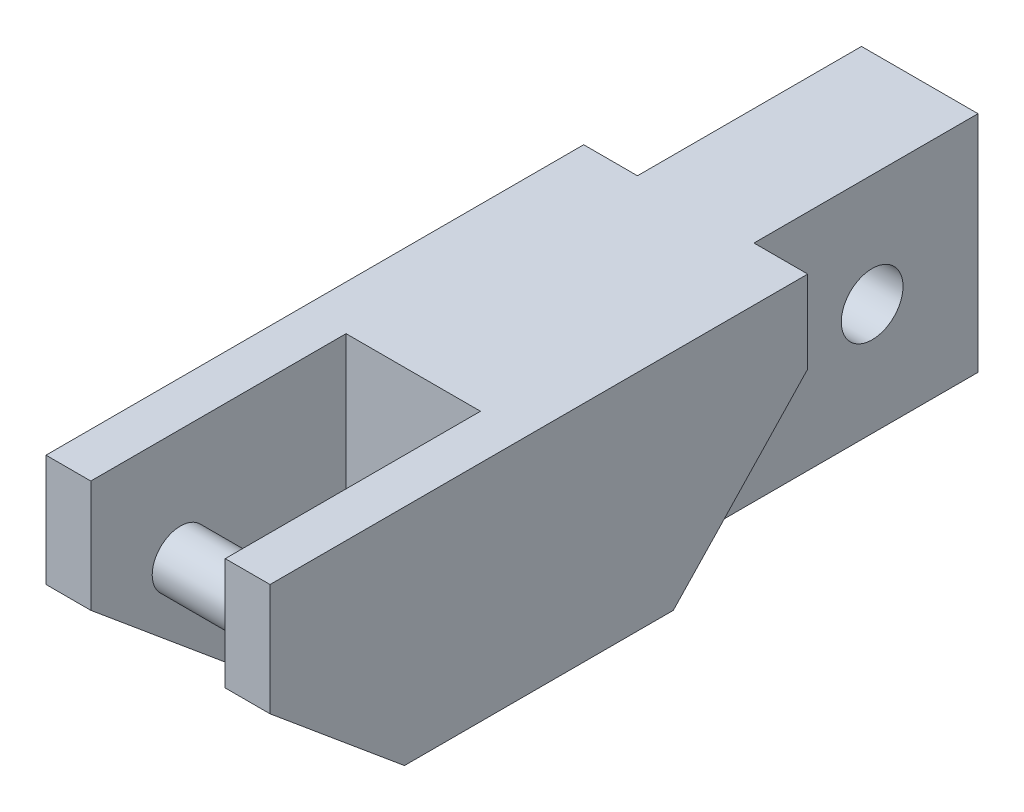
SolidWorks part; units mm, degrees
ref_plane "Front Plane" through (0, 0, 0) normal (0, 0, 1) x (1, 0, 0)
ref_plane "Top Plane" through (0, 0, 0) normal (0, 1, 0) x (1, 0, 0)
ref_plane "Right Plane" through (0, 0, 0) normal (1, 0, 0) x (0, 0, -1)
sketch "Sketch2" plane through (0, 0, 0) normal (0, 1, 0) x (1, 0, 0)
  line L0 (-31.2782, 12.0242) -> (-18.5782, 12.0242)
  line L1 (-28.2302, 24.7242) -> (-21.6262, 24.7242)
  line L2 (-31.2782, 12.0242) -> (-31.2782, -18.4558)
  line L3 (-31.2782, -18.4558) -> (-28.7382, -18.4558)
  line L4 (-18.5782, 12.0242) -> (-18.5782, -18.4558)
  line L5 (-28.2302, 24.7242) -> (-28.2302, 12.0242)
  line L6 (-21.6262, 24.7242) -> (-21.6262, 12.0242)
  line L7 (-28.7382, -18.4558) -> (-28.7382, -3.9858)
  line L8 (-28.7382, -3.9858) -> (-21.1182, -3.9858)
  line L9 (-21.1182, -3.9858) -> (-21.1182, -18.4558)
  line L10 (-31.2782, -3.9858) -> (-18.5782, -3.9858)
  line L11 (-21.1182, -18.4558) -> (-18.5782, -18.4558)
  line L12 (-28.2302, 12.0242) -> (-21.6262, 12.0242)
  dimension "D1" = 43.18
  dimension "D2" = 12.7
  dimension "D3" = 2.54
  dimension "D4" = 2.54
  dimension "D5" = 3.048
  dimension "D6" = 3.048
  dimension "D7" = 12.7
  dimension "D8" = 14.47
extrude "Boss-Extrude1" add sketch "Sketch2" along normal blind 12.7 contours L2 L10 L8 L4 L0 | L6 L1 L5 L0 | L9 L11 L4 L10 | L10 L2 L3 L7 region at (-24.9282, 0, -4.0192) region at (-24.9282, 0, -18.3742) region at (-30.0082, 0, 11.2208) region at (-19.8482, 0, 11.2208)
sketch "Sketch3" plane through (0, 0, 0) normal (1, 0, 0) x (0, 0, -1)
  line L0 (-13.3758, 12.7) -> (-13.3758, 0) construction
  line L1 (12.0242, 12.7) -> (-18.4558, 12.7) construction
  line L2 (12.0242, 0) -> (-18.4558, 0) construction
  line L3 (-18.4558, 12.7) -> (-18.4558, 0) construction
  line L4 (-18.4558, 6.35) -> (24.7242, 6.35) construction
  line L5 (24.7242, 12.7) -> (24.7242, 0) construction
  line L6 (18.7242, 12.7) -> (18.7242, 0) construction
  line L7 (24.7242, 12.7) -> (12.0242, 12.7) construction
  line L8 (24.7242, 0) -> (12.0242, 0) construction
  circle A0 centre (-13.3758, 6.35) radius 1.6
  circle A1 centre (18.7242, 6.35) radius 1.75
  dimension "D1" = 5.08
  dimension "D2" = 6
extrude "Cut-Extrude1" cut sketch "Sketch3" against normal through all contours A1
extrude "Boss-Extrude4" add sketch "Sketch3<3>" against normal through all from surface contours A0 starting at face at (-18.5782, 6.35, 3.2158)
sketch "Sketch3<3>" plane through (0, 0, 0) normal (1, 0, 0) x (0, 0, -1) same geometry as "Sketch3"
sketch "Sketch29" plane through (-18.5782, 0, 0) normal (1, 0, 0) x (0, 0, -1)
  line L0 (-18.4373, 6.3346) -> (38392.6267, -32002.8854) construction
  line L1 (-18.4558, 12.7) -> (-18.4558, 0) construction
  line L3 (-18.4558, 6.35) -> (-10.8358, 0)
  line L4 (-10.8358, 0) -> (-18.4558, 0)
  line L5 (-18.4558, 0) -> (-18.4558, 6.35)
  point P4 (-18.4558, 6.35)
  dimension "D1" = 7.62
extrude "Cut-Extrude12" cut sketch "Sketch29" against normal through all
sketch "Sketch31" plane through (-18.5782, 0, 0) normal (1, 0, 0) x (0, 0, -1)
  line L0 (11.3283, 6.6241) -> (-36118.149, -34557.2425) construction
  line L2 (12.0242, 8.0398) -> (4.4042, 0)
  line L3 (4.4042, 0) -> (12.0242, 0)
  line L4 (12.0242, 0) -> (12.0242, 8.0398)
  dimension "D1" = 7.62
  dimension "D2" = 8.0398
extrude "Cut-Extrude14" cut sketch "Sketch31" against normal up to surface (3.048 mm away) up to face at (-21.6262, 6.35, -20.4742)
sketch "Sketch37" plane through (0, 0, 0) normal (0, -1, 0) x (1, 0, 0)
  line L0 (-24.9282, 3.9858) -> (-24.9282, -24.7242) construction
  line L1 (-28.7382, 3.9858) -> (-21.1182, 3.9858) construction
  line L2 (-28.2302, -24.7242) -> (-21.6262, -24.7242) construction
  line L4 (-25.7282, 3.9858) -> (-24.1282, 3.9858)
  line L5 (-25.7282, 3.9858) -> (-25.7282, -24.7242)
  line L6 (-25.7282, -24.7242) -> (-24.1282, -24.7242)
  line L7 (-24.1282, 3.9858) -> (-24.1282, -24.7242)
  dimension "D1" = 0.8
  dimension "D2" = 0.8
extrude "Cut-Extrude17" cut sketch "Sketch37" against normal blind 3.175
sketch "Sketch38" plane through (0, 0, 0) normal (0, -1, 0) x (1, 0, 0)
  line L0 (-18.5782, -4.4042) -> (-31.2782, -4.4042) construction
  line L1 (-31.2782, -12.0242) -> (-31.2782, 10.8358) construction
  line L3 (-25.7282, 3.9858) -> (-24.0504, 3.9858)
  line L4 (-25.7282, 3.9858) -> (-25.7282, -4.4042)
  line L5 (-25.7282, -4.4042) -> (-24.0504, -4.4042)
  line L6 (-24.0504, 3.9858) -> (-24.0504, -4.4042)
extrude "Boss-Extrude7" add sketch "Sketch38" against normal blind 1.5875
equation "\"0..25in\"=0.2"
